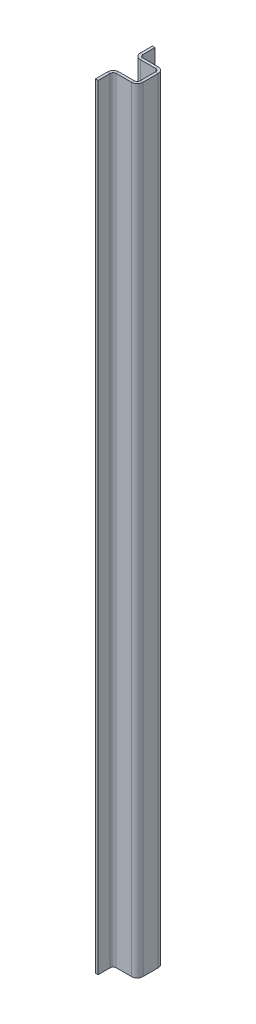
SolidWorks part; units mm, degrees
note: The reader was unsure of these and kept them because the rebuilt part matched: flange length of "Edge-Flange1", "Edge-Flange2".
material "1023 Carbon Steel Sheet (SS)"
ref_plane "Front Plane" through (0, 0, 0) normal (0, 0, 1) x (1, 0, 0)
ref_plane "Top Plane" through (0, 0, 0) normal (0, 1, 0) x (1, 0, 0)
ref_plane "Right Plane" through (0, 0, 0) normal (1, 0, 0) x (0, 0, -1)
sketch "Sketch2" plane through (0, 0, 0) normal (1, 0, 0) x (0, 0, -1)
  line L1 (-9.525, 276.733) -> (9.525, 276.733)
  line L2 (-9.525, 276.733) -> (-9.525, -276.733)
  line L3 (-9.525, -276.733) -> (9.525, -276.733)
  line L4 (9.525, 276.733) -> (9.525, -276.733)
  line L5 (-9.525, 276.733) -> (9.525, -276.733) construction
  line L6 (-9.525, -276.733) -> (9.525, 276.733) construction
  point P0 (0, 0)
  dimension "D1" = 553.466
  dimension "D2" = 19.05
base flange "Base-Flange1" sketch "Sketch2" thickness 1.8974 reverse thickness direction no parameters "D1"=2.54
edge flange "Edge-Flange1" sketch "Sketch9" flange profiles "Sketch9", "Sketch11" flange angle 90 flange length 19.05 flange position material inside bend radius 2.159 thickness 1.8974 relief rectangular parameters "D6"=10, "D8"=0.254
sketch "Sketch9" plane through (-1.8974, 0, 9.525) normal (0, 0, 1) x (0, 1, 0)
  line L2 (-276.733, 0) -> (-276.733, 17.1526)
  line L3 (-276.733, 17.1526) -> (276.733, 17.1526)
  line L4 (276.733, 17.1526) -> (276.733, 0)
  line L7 (276.733, 0) -> (-276.733, 0) construction
  line L8 (276.733, 0) -> (-276.733, 0)
sketch "Sketch11" plane through (-1.8974, 0, -9.525) normal (0, 0, -1) x (0, -1, 0)
  line L0 (276.733, 0) -> (-276.733, 0) construction
  line L1 (276.733, 0) -> (-276.733, 0)
  line L2 (-276.733, 0) -> (-276.733, 17.1526)
  line L3 (-276.733, 17.1526) -> (276.733, 17.1526)
  line L4 (276.733, 17.1526) -> (276.733, 0)
bend "EdgeBend1" bend radius 2.159 bend angle 90 parameters "D5"=1
bend "EdgeBend2" bend radius 2.159 bend angle 90 parameters "D5"=3
edge flange "Edge-Flange2" sketch "Sketch16" flange profiles "Sketch16", "Sketch17" flange angle 90 flange length 12.7 flange position material inside bend radius 2.159 thickness 1.8974 relief rectangular parameters "D6"=10, "D8"=0.254
sketch "Sketch16" plane through (-19.05, 0, -9.525) normal (-1, 0, 0) x (0, 1, 0)
  line L2 (-276.733, 0) -> (-276.733, 10.8026)
  line L3 (-276.733, 10.8026) -> (276.733, 10.8026)
  line L4 (276.733, 10.8026) -> (276.733, 0)
  line L7 (-276.733, 0) -> (276.733, 0) construction
  line L8 (-276.733, 0) -> (276.733, 0)
sketch "Sketch17" plane through (-19.05, 0, 9.525) normal (-1, 0, 0) x (0, -1, 0)
  line L0 (-276.733, 0) -> (276.733, 0) construction
  line L1 (-276.733, 0) -> (276.733, 0)
  line L2 (-276.733, 0) -> (-276.733, 10.8026)
  line L3 (-276.733, 10.8026) -> (276.733, 10.8026)
  line L4 (276.733, 10.8026) -> (276.733, 0)
bend "EdgeBend3" bend radius 2.159 bend angle 90 parameters "D5"=4
bend "EdgeBend4" bend radius 2.159 bend angle 90 parameters "D5"=5
sketch "Bend-Lines1" [suppressed] plane through (0, 0, 0) normal (0, 1, 0) x (1, 0, 0)
sketch "Bounding-Box1" [suppressed] plane through (0, 0, 0) normal (0, 1, 0) x (1, 0, 0)
sheet metal parameters "Sheet-Metal1" thickness 1.8974 parameters "D1"=3.175
flat pattern "Flat-Pattern1" [suppressed]
sketch "Bend-Lines2" plane through (0, 0, 0) normal (0, 1, 0) x (1, 0, 0)
sketch3d "Bounding-Box2" [suppressed]
  line L0 (-9.525, 276.733, 0) -> (-9.525, -276.733, 0) construction
  line L1 (9.525, 276.733, 0) -> (9.525, -276.733, 0) construction
  line L2 (-9.525, 276.733, 0) -> (9.525, 276.733, 0) construction
  line L3 (-9.525, -276.733, 0) -> (9.525, -276.733, 0) construction
sheet metal parameters "Sheet-Metal2" thickness 1.8974 parameters "D1"=3.175
flat pattern "Flat-Pattern1"
sketch "Bend-Lines2" plane through (0, 0, 0) normal (1, 0, 0) x (0, 0, -1)
  line L0 (-7.2301, 276.733) -> (-7.2301, -276.733) construction
  line L1 (-7.2301, 276.733) -> (-7.2301, -276.733) construction
  line L2 (7.2301, -276.733) -> (7.2301, 276.733) construction
  line L3 (7.2301, -276.733) -> (7.2301, 276.733) construction
sketch3d "Bounding-Box2" [suppressed]
  line L0 (23.9853, 276.733, 0) -> (23.9853, -276.733, 0) construction
  line L1 (-23.9853, 276.733, 0) -> (-23.9853, -276.733, 0) construction
  line L2 (23.9853, 276.733, 0) -> (-23.9853, 276.733, 0) construction
  line L3 (23.9853, -276.733, 0) -> (-23.9853, -276.733, 0) construction
bend of the flat pattern "Flatten-<EdgeBend1>1"
bend of the flat pattern "Flatten-<EdgeBend2>1"
sheet metal parameters "Sheet-Metal3" thickness 1.8974 parameters "D1"=3.175
flat pattern "Flat-Pattern1"
sketch "Bend-Lines2" plane through (0, 0, 0) normal (1, 0, 0) x (0, 0, -1)
  line L0 (-7.9094, 276.733) -> (-7.9094, -276.733) construction
  line L1 (-7.9094, 276.733) -> (-7.9094, -276.733) construction
  line L2 (7.9094, -276.733) -> (7.9094, 276.733) construction
  line L3 (7.9094, -276.733) -> (7.9094, 276.733) construction
  line L4 (-23.7282, 276.733) -> (-23.7282, -276.733) construction
  line L5 (23.7282, -276.733) -> (23.7282, 276.733) construction
  line L6 (-23.7282, 276.733) -> (-23.7282, -276.733) construction
  line L7 (23.7282, -276.733) -> (23.7282, 276.733) construction
sketch3d "Bounding-Box2" [suppressed]
  line L0 (34.8126, 276.733, 0) -> (34.8126, -276.733, 0) construction
  line L1 (-34.8126, 276.733, 0) -> (-34.8126, -276.733, 0) construction
  line L2 (34.8126, 276.733, 0) -> (-34.8126, 276.733, 0) construction
  line L3 (34.8126, -276.733, 0) -> (-34.8126, -276.733, 0) construction
bend of the flat pattern "Flatten-<EdgeBend1>1"
bend of the flat pattern "Flatten-<EdgeBend2>1"
bend of the flat pattern "Flatten-<EdgeBend3>1"
bend of the flat pattern "Flatten-<EdgeBend4>1"
